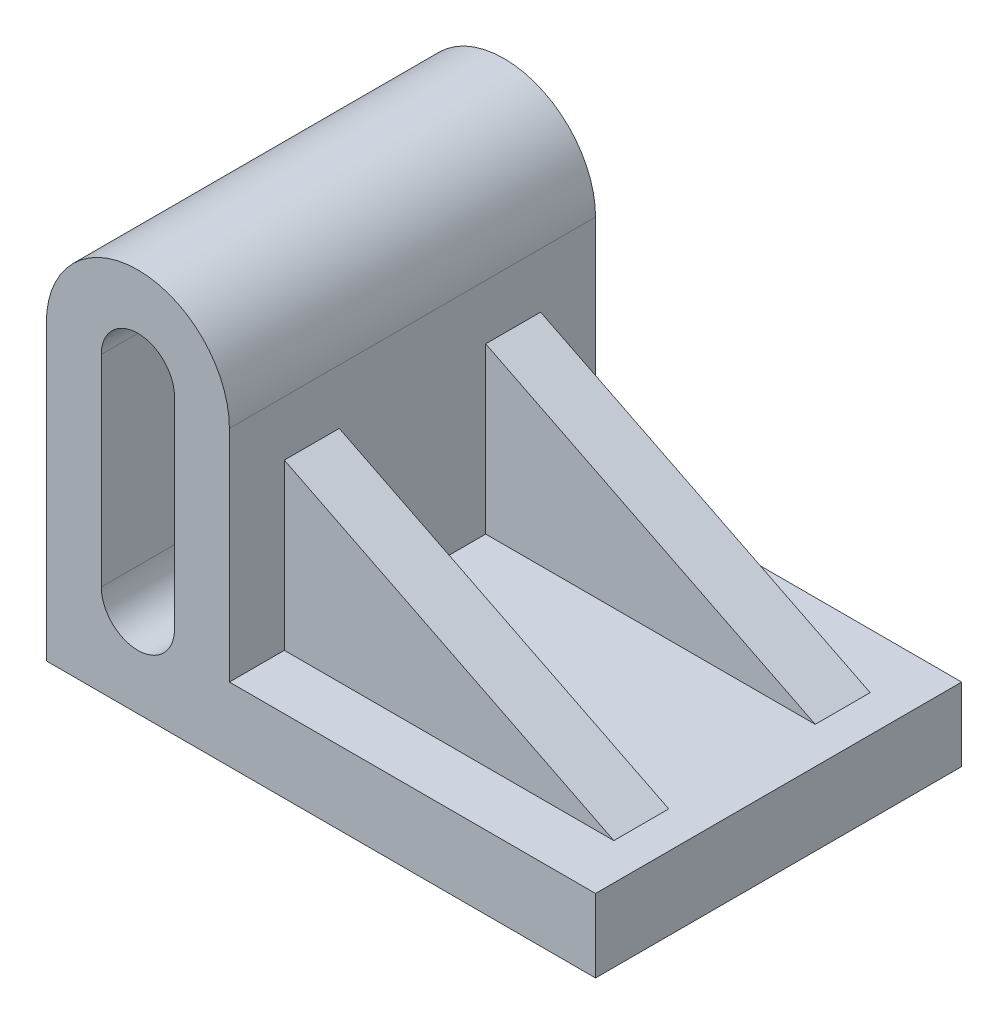
SolidWorks part; units mm, degrees
ref_plane "Front Plane" through (0, 0, 0) normal (0, 0, 1) x (1, 0, 0)
ref_plane "Top Plane" through (0, 0, 0) normal (0, 1, 0) x (1, 0, 0)
ref_plane "Right Plane" through (0, 0, 0) normal (1, 0, 0) x (0, 0, -1)
sketch "Sketch1" plane through (0, 0, 0) normal (0, 0, 1) x (1, 0, 0)
  line L0 (0, 0) -> (150, 0)
  line L1 (150, 0) -> (150, 20)
  line L2 (150, 20) -> (50, 20)
  line L3 (50, 20) -> (50, 80)
  line L5 (0, 80) -> (0, 0)
  arc A0 (50, 80) -> (0, 80) centre (25, 80) ccw
  dimension "D1" = 50
  dimension "D2" = 20
  dimension "D3" = 80
  dimension "D4" = 100
extrude "Boss-Extrude1" add sketch "Sketch1" along normal blind 50 and the other way blind 50
sketch "Sketch2" plane through (0, 0, 50) normal (0, 0, 1) x (1, 0, 0)
  line L0 (25, 80) -> (25, 25) construction
  line L3 (35, 80) -> (35, 25)
  line L4 (15, 80) -> (15, 25)
  arc A4 (35, 80) -> (15, 80) centre (25, 80) ccw
  arc A5 (15, 25) -> (35, 25) centre (25, 25) ccw
  arc A6 (50, 80) -> (0, 80) centre (25, 80) ccw construction
  point P3 (25, 52.5)
  dimension "D1" = 10
  dimension "D2" = 55
extrude "Cut-Extrude1" cut sketch "Sketch2" against normal through all
sketch "Sketch3" plane through (0, 0, 0) normal (0, 0, 1) x (1, 0, 0)
  line L0 (50, 65) -> (50, 20)
  line L1 (50, 20) -> (140, 20)
  line L2 (140, 20) -> (50, 65)
  line L3 (50, 20) -> (50, 80) construction
  line L4 (150, 20) -> (50, 20) construction
  point P7 (0, 0)
  dimension "D1" = 10
  dimension "D2" = 45
extrude "Boss-Extrude2" add sketch "Sketch3" along normal blind 35 and the other way blind 35
sketch "Sketch4" plane through (0, 20, 0) normal (0, 1, 0) x (1, 0, 0)
  line L0 (50, 35) -> (50, -35) construction
  line L1 (50, 20) -> (150, 20)
  line L2 (50, 20) -> (50, -20)
  line L3 (50, -20) -> (150, -20)
  line L4 (150, 20) -> (150, -20)
  line L5 (-57.75, 0) -> (57.75, 0) construction
  dimension "D1" = 100
  dimension "D2" = 20
  dimension "D3" = 20
extrude "Cut-Extrude2" cut sketch "Sketch4" along normal through all
